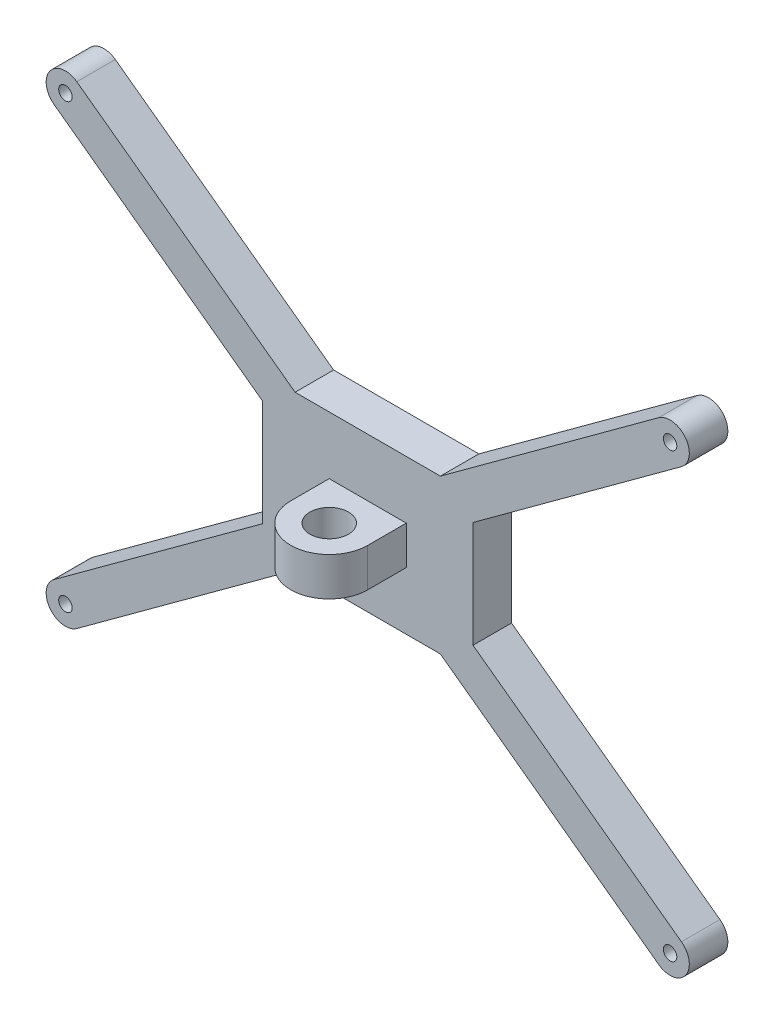
SolidWorks part; units mm, degrees
other "Marquage1"
sketch "Esquisse3" plane through (-5, -5, 30) normal (0, 0, 1) x (1, 0, 0)
ref_plane "Plan de face" through (0, 0, 0) normal (0, 0, 1) x (1, 0, 0)
ref_plane "Plan de dessus" through (0, 0, 0) normal (0, 1, 0) x (1, 0, 0)
ref_plane "Plan de droite" through (0, 0, 0) normal (1, 0, 0) x (0, 0, -1)
sketch "Esquisse1" plane through (0, 0, 0) normal (0, 0, 1) x (1, 0, 0)
  line L0 (-2.9529, 110.8651) -> (51.1719, 71.254)
  line L1 (0, 0) -> (157, 0) construction
  line L2 (0, 0) -> (0, 114.9) construction
  line L3 (0, 114.9) -> (157, 114.9) construction
  line L4 (157, 0) -> (157, 114.9) construction
  line L5 (59.6381, 37.45) -> (97.3619, 37.45)
  line L6 (51.1719, 43.646) -> (51.1719, 71.254)
  line L7 (59.6381, 77.45) -> (97.3619, 77.45)
  line L8 (105.8281, 43.646) -> (105.8281, 71.254)
  line L9 (74.2669, 54.352) -> (78.5, 57.45) construction
  line L10 (74.2669, 60.548) -> (78.5, 57.45) construction
  line L11 (2.9529, 118.9349) -> (59.6381, 77.45)
  line L12 (154.0471, 118.9349) -> (97.3619, 77.45)
  line L13 (159.9529, 110.8651) -> (105.8281, 71.254)
  line L14 (86.9662, 57.45) -> (105.8281, 43.646) construction
  line L15 (105.8281, 43.646) -> (159.9529, 4.0349)
  line L16 (82.7331, 54.352) -> (105.8281, 37.45) construction
  line L17 (78.5, 51.254) -> (97.3619, 37.45) construction
  line L18 (97.3619, 37.45) -> (154.0471, -4.0349)
  line L19 (78.5, 51.254) -> (59.6381, 37.45) construction
  line L20 (59.6381, 37.45) -> (2.9529, -4.0349)
  line L21 (51.1719, 37.45) -> (74.2669, 54.352) construction
  line L22 (70.0338, 57.45) -> (51.1719, 43.646) construction
  line L23 (51.1719, 43.646) -> (-2.9529, 4.0349)
  line L24 (51.1719, 71.254) -> (70.0338, 57.45) construction
  line L25 (70.0338, 57.45) -> (74.2669, 54.352) construction
  line L26 (51.1719, 77.45) -> (74.2669, 60.548) construction
  line L27 (59.6381, 77.45) -> (78.5, 63.646) construction
  line L28 (78.5, 63.646) -> (82.7331, 60.548) construction
  line L29 (97.3619, 77.45) -> (78.5, 63.646) construction
  line L30 (74.2669, 60.548) -> (70.0338, 57.45) construction
  line L31 (82.7331, 60.548) -> (105.8281, 77.45) construction
  line L32 (105.8281, 71.254) -> (86.9662, 57.45) construction
  line L33 (82.7331, 54.352) -> (78.5, 51.254) construction
  line L34 (82.7331, 60.548) -> (86.9662, 57.45) construction
  line L35 (78.5, 57.45) -> (82.7331, 60.548) construction
  line L36 (78.5, 63.646) -> (74.2669, 60.548) construction
  line L37 (86.9662, 57.45) -> (82.7331, 54.352) construction
  line L38 (74.2669, 54.352) -> (78.5, 51.254) construction
  line L39 (78.5, 57.45) -> (82.7331, 54.352) construction
  line L40 (105.8281, 37.45) -> (105.8281, 43.646) construction
  line L41 (97.3619, 37.45) -> (105.8281, 37.45) construction
  line L42 (51.1719, 37.45) -> (59.6381, 37.45) construction
  line L43 (51.1719, 37.45) -> (51.1719, 43.646) construction
  line L44 (105.8281, 71.254) -> (105.8281, 77.45) construction
  line L45 (97.3619, 77.45) -> (105.8281, 77.45) construction
  line L46 (51.1719, 77.45) -> (59.6381, 77.45) construction
  line L47 (51.1719, 71.254) -> (51.1719, 77.45) construction
  circle A0 centre (0, 0) radius 1.75
  circle A1 centre (0, 114.9) radius 1.75
  circle A2 centre (157, 0) radius 1.75
  circle A3 centre (157, 114.9) radius 1.75
  arc A4 (2.9529, 118.9349) -> (-2.9529, 110.8651) centre (0, 114.9) ccw
  arc A5 (-2.9529, 4.0349) -> (2.9529, -4.0349) centre (0, 0) ccw
  arc A6 (154.0471, -4.0349) -> (159.9529, 4.0349) centre (157, 0) ccw
  arc A7 (159.9529, 110.8651) -> (154.0471, 118.9349) centre (157, 114.9) ccw
  arc A8 (5, 0) -> (0, 5) centre (0, 0) ccw construction
  arc A9 (0, 109.9) -> (5, 114.9) centre (0, 114.9) ccw construction
  arc A10 (152, 114.9) -> (157, 109.9) centre (157, 114.9) ccw construction
  arc A11 (157, 5) -> (152, 0) centre (157, 0) ccw construction
  arc A12 (-2.9529, 110.8651) -> (0, 109.9) centre (0, 114.9) ccw construction
  arc A13 (5, 114.9) -> (2.9529, 118.9349) centre (0, 114.9) ccw construction
  arc A14 (154.0471, 118.9349) -> (152, 114.9) centre (157, 114.9) ccw construction
  arc A15 (157, 109.9) -> (159.9529, 110.8651) centre (157, 114.9) ccw construction
  arc A16 (159.9529, 4.0349) -> (157, 5) centre (157, 0) ccw construction
  arc A17 (152, 0) -> (154.0471, -4.0349) centre (157, 0) ccw construction
  arc A18 (2.9529, -4.0349) -> (5, 0) centre (0, 0) ccw construction
  arc A19 (0, 5) -> (-2.9529, 4.0349) centre (0, 0) ccw construction
  point P9 (78.5, 57.45)
  point P14 (78.5, 114.9)
  point P15 (0, 57.45)
  point P28 (0, 0)
  point P50 (0, 0)
  dimension "D3" = 3.5
  dimension "D4" = 10
  dimension "D1" = 157
  dimension "D2" = 114.9
  dimension "D5" = 40
extrude "Boss.-Extru.1" add sketch "Esquisse1" along normal blind 10
sketch "Esquisse2" plane through (51.1719, 158.8108, 0) normal (1, 0, 0) x (0, 0, 1)
  line L0 (10, 111.3608) -> (20, 111.3608)
  line L1 (20, 111.3608) -> (20, 91.3608) construction
  line L2 (20, 91.3608) -> (10, 91.3608)
  line L3 (10, 111.3608) -> (10, 91.3608)
  line L4 (10, 115.1649) -> (10, 87.5568) construction
  circle A0 centre (20, 101.3608) radius 5
  arc A1 (20, 111.3608) -> (20, 91.3608) centre (20, 101.3608) cw
  point P0 (10, 49.4054)
  point P7 (10, 101.3608)
  point P12 (10, 101.3608)
  dimension "D2" = 10
  dimension "D1" = 10
  dimension "D3" = 20
extrude "Boss.-Extru.2" [suppressed] add sketch "Esquisse2" along normal blind 10 from offset 25
sketch "Esquisse4" plane through (0, 37.45, 123.3162) normal (0, 1, 0) x (1, 0, 0)
  line L0 (88.5, 113.3162) -> (88.5, 103.3162)
  line L1 (97.3619, 113.3162) -> (59.6381, 113.3162) construction
  line L2 (68.5, 103.3162) -> (68.5, 113.3162)
  line L3 (88.5, 113.3162) -> (68.5, 113.3162)
  line L4 (59.6381, 113.3162) -> (2.9529, 113.3162) construction
  line L5 (68.5, 103.3162) -> (88.5, 103.3162) construction
  circle A0 centre (78.5, 103.3162) radius 5
  arc A1 (88.5, 103.3162) -> (68.5, 103.3162) centre (78.5, 103.3162) cw
  point P9 (78.5, 113.3162)
  point P12 (78.5, 113.3162)
  dimension "D2" = 10
  dimension "D1" = 10
  dimension "D3" = 20
extrude "Boss.-Extru.3" add sketch "Esquisse4" along normal blind 10 from offset 15
ref_axis "Axe1" through (78.5, 62.45, 20) along (0, -1, 0)
ref_plane "Plan1" through (78.5, 0, 0) normal (-1, 0, 0) x (0, 0, 1)
ref_axis "Axe2" [suppressed] through (83.5, 57.45, 20) along (-1, 0, 0)
ref_plane "Plan2" [suppressed] through (0, 57.45, 0) normal (0, 1, 0) x (1, 0, 0)
